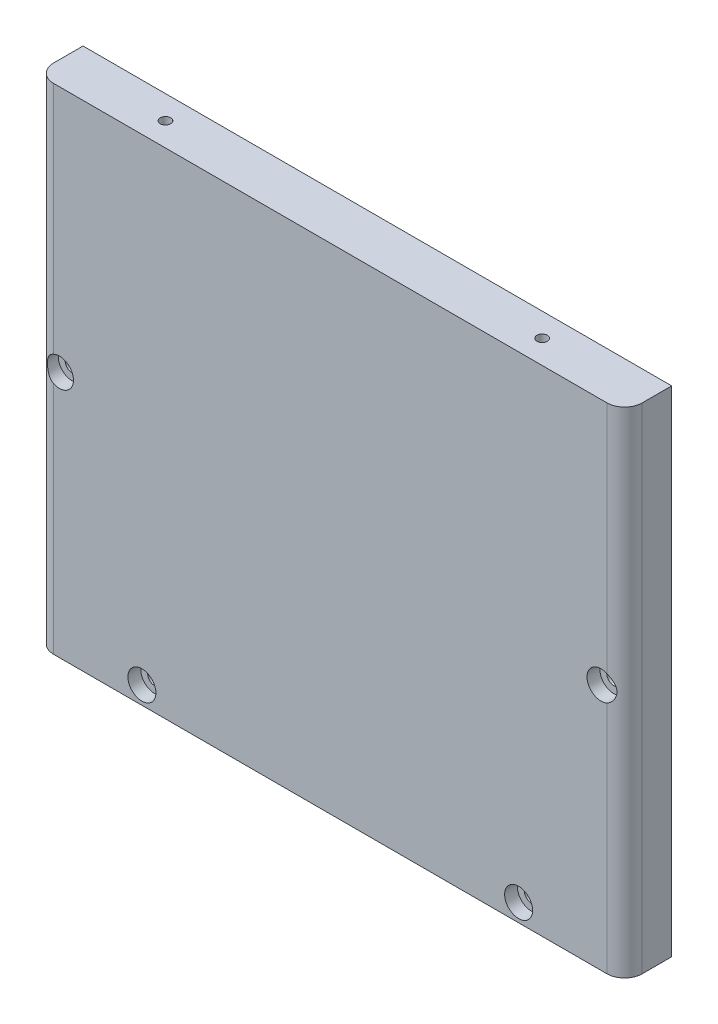
SolidWorks part; units mm, degrees
ref_plane "Front Plane" through (0, 0, 0) normal (0, 0, 1) x (1, 0, 0)
ref_plane "Top Plane" through (0, 0, 0) normal (0, 1, 0) x (1, 0, 0)
ref_plane "Right Plane" through (0, 0, 0) normal (1, 0, 0) x (0, 0, -1)
sketch "Sketch1" plane through (0, 0, 0) normal (0, 0, 1) x (1, 0, 0)
  line L1 (-50, 42) -> (50, 42)
  line L2 (-50, 42) -> (-50, -42)
  line L3 (-50, -42) -> (50, -42)
  line L4 (50, 42) -> (50, -42)
  line L5 (-50, 42) -> (50, -42) construction
  line L6 (-50, -42) -> (50, 42) construction
  point P0 (0, 0)
extrude "Boss-Extrude1" add sketch "Sketch1" along normal blind 8
sketch "Sketch2" plane through (0, 0, 8) normal (0, 0, 1) x (1, 0, 0)
  line L0 (-50, -42) -> (-50, -36) construction
  line L1 (-50, -36) -> (50, -36) construction
  line L2 (50, -42) -> (50, 42) construction
  line L3 (50, -36) -> (50, -42) construction
  line L4 (-50, -39) -> (-32, -39) construction
  line L5 (50, -39) -> (32, -39) construction
hole_wizard "CBORE for #2 Socket Head Cap Screw1" positions "3DSketch1" profile "Sketch3" counterbore size "#2" standard "ANSI Inch"
sketch3d "3DSketch1"
  point P0 (-32, -39, 8)
  point P3 (32, -39, 8)
sketch "Sketch3" plane through (-32, -39, 8) normal (1, 0, 0) x (0, -1, 0)
  line L0 (0, 0) -> (0, 13.0026)
  line L1 (0, 13.0026) -> (1.2192, 12.27)
  line L2 (1.2192, 12.27) -> (1.2192, 2.1844)
  line L3 (1.2192, 2.1844) -> (2.3812, 2.1844)
  line L4 (2.3812, 2.1844) -> (2.3812, 0)
  line L5 (2.3812, 0) -> (0, 0)
  line L10 (0, 13.0026) -> (-1.2192, 12.27) construction
  line L11 (0, -6.35) -> (0, 107.95) construction
  dimension "Hole Dia." = 2.4384
  dimension "Hole Depth" = 12.27
  dimension "C'Bore Dia." = 4.7625
  dimension "C'Bore Depth" = 2.1844
  dimension "Drill Angle" = 118
sketch "Sketch4" plane through (0, 0, 8) normal (0, 0, 1) x (1, 0, 0)
  line L0 (-50, -42) -> (-42, -42) construction
  line L1 (-42, -42) -> (-42, 42) construction
  line L2 (50, 42) -> (-50, 42) construction
  line L3 (-42, 42) -> (-50, 42) construction
  line L4 (50, -42) -> (42, -42) construction
  line L5 (42, -42) -> (42, 42) construction
  line L6 (42, 42) -> (50, 42) construction
  line L7 (46, -42) -> (46, 0) construction
  line L8 (-46, -42) -> (-46, 0) construction
hole_wizard "CBORE for #2 Socket Head Cap Screw2" positions "3DSketch2" profile "Sketch5" counterbore size "#2" standard "ANSI Inch"
sketch3d "3DSketch2"
  point P0 (-46, 0, 8)
  point P3 (46, 0, 8)
sketch "Sketch5" plane through (-46, 0, 8) normal (1, 0, 0) x (0, -1, 0)
  line L0 (0, 0) -> (0, 13.0026)
  line L1 (0, 13.0026) -> (1.2192, 12.27)
  line L2 (1.2192, 12.27) -> (1.2192, 2.1844)
  line L3 (1.2192, 2.1844) -> (2.3812, 2.1844)
  line L4 (2.3812, 2.1844) -> (2.3812, 0)
  line L5 (2.3812, 0) -> (0, 0)
  line L10 (0, 13.0026) -> (-1.2192, 12.27) construction
  line L11 (0, -6.35) -> (0, 107.95) construction
  dimension "Hole Dia." = 2.4384
  dimension "Hole Depth" = 12.27
  dimension "C'Bore Dia." = 4.7625
  dimension "C'Bore Depth" = 2.1844
  dimension "Drill Angle" = 118
sketch "Sketch6" plane through (0, 42, 0) normal (0, 1, 0) x (1, 0, 0)
  line L0 (-50, -4) -> (-32, -4) construction
  line L1 (-50, -8) -> (-50, 0) construction
  line L2 (50, -4) -> (32, -4) construction
  line L3 (50, -8) -> (50, 0) construction
hole_wizard "#2-56 Tapped Hole1" positions "3DSketch3" profile "Sketch7" tap size "#2-56" standard "ANSI Inch"
sketch3d "3DSketch3"
  point P0 (-32, 42, 4)
  point P3 (32, 42, 4)
sketch "Sketch7" plane through (-32, 42, 4) normal (1, 0, 0) x (0, 0, 1)
  line L0 (0, 0) -> (0, 12.5342)
  line L1 (0, 12.5342) -> (0.889, 12)
  line L2 (0.889, 12) -> (0.889, 0)
  line L5 (0.889, 0) -> (0, 0)
  line L10 (0, 12.5342) -> (-0.889, 12) construction
  line L11 (0, -6.35) -> (0, 107.95) construction
  dimension "Tap Drill Dia." = 1.778
  dimension "Tap Drill Depth" = 12
  dimension "Drill Angle" = 118
cosmetic thread "Hole Thread1" parameters "D1"=10, "D2"=2.1844
cosmetic thread "Hole Thread2" parameters "D1"=10, "D2"=2.1844
fillet "Fillet1" radius 3 2 edges at (50, 0, 8) (-50, 0, 8)
